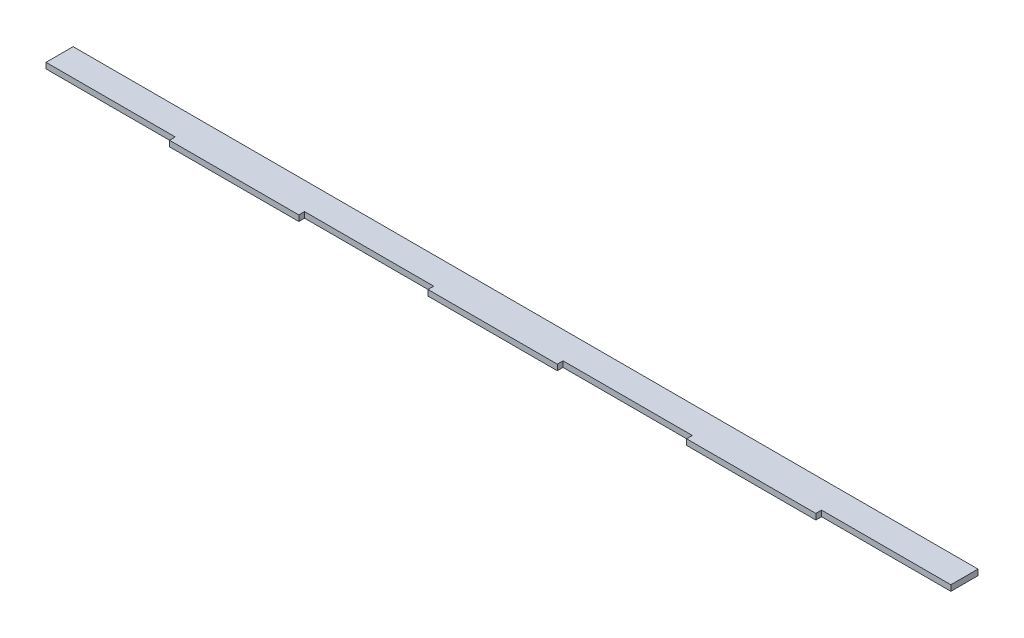
SolidWorks part; units mm, degrees
ref_plane "Front Plane" through (0, 0, 0) normal (0, 0, 1) x (1, 0, 0)
ref_plane "Top Plane" through (0, 0, 0) normal (0, 1, 0) x (1, 0, 0)
ref_plane "Right Plane" through (0, 0, 0) normal (1, 0, 0) x (0, 0, -1)
sketch "Sketch1" plane through (0, 0, 0) normal (0, 1, 0) x (1, 0, 0)
  line L24 (478.5571, -3.175) -> (478.5571, 0) construction
  line L32 (-21.4429, 0) -> (-21.4429, 15)
  line L33 (478.5571, 0) -> (478.5571, 15)
  line L34 (478.5571, 15) -> (-21.4429, 15)
  line L42 (478.5571, -3.175) -> (478.5571, 0) construction
  line L44 (407.1286, -3.175) -> (407.1286, 0) construction
  line L45 (335.7, -3.175) -> (335.7, 0) construction
  line L46 (264.2714, -3.175) -> (264.2714, 0) construction
  line L47 (192.8429, -3.175) -> (192.8429, 0) construction
  line L48 (121.4143, -3.175) -> (121.4143, 0) construction
  line L49 (49.9857, -3.175) -> (49.9857, 0) construction
  line L50 (407.1286, -3.175) -> (407.1286, 0)
  line L51 (335.7, -3.175) -> (335.7, 0)
  line L52 (264.2714, -3.175) -> (264.2714, 0)
  line L53 (192.8429, -3.175) -> (192.8429, 0)
  line L54 (121.4143, -3.175) -> (121.4143, 0)
  line L55 (49.9857, -3.175) -> (49.9857, 0)
  line L56 (-21.4429, 0) -> (49.9857, 0)
  line L57 (49.9857, -3.175) -> (121.4143, -3.175)
  line L58 (121.4143, 0) -> (192.8429, 0)
  line L59 (192.8429, -3.175) -> (264.2714, -3.175)
  line L60 (264.2714, 0) -> (335.7, 0)
  line L61 (335.7, -3.175) -> (407.1286, -3.175)
  line L62 (407.1286, 0) -> (478.5571, 0)
  dimension "D1" = 15
  dimension "D2" = 15
extrude "Boss-Extrude1" add sketch "Sketch1" along normal blind 3.175
